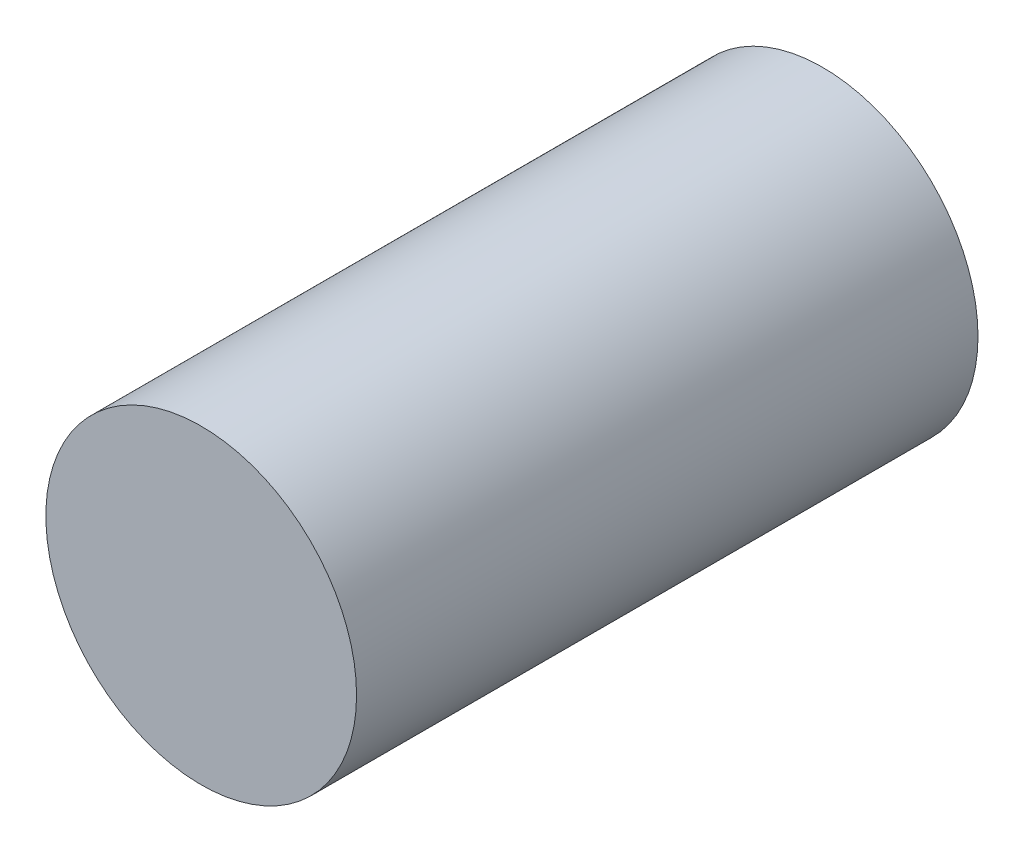
SolidWorks part; units mm, degrees
ref_plane "Front Plane" through (0, 0, 0) normal (0, 0, 1) x (1, 0, 0)
ref_plane "Top Plane" through (0, 0, 0) normal (0, 1, 0) x (1, 0, 0)
ref_plane "Right Plane" through (0, 0, 0) normal (1, 0, 0) x (0, 0, -1)
sketch "Sketch1" plane through (0, 0, 0) normal (0, 0, 1) x (1, 0, 0)
  circle A0 centre (0, 0) radius 12.5
  dimension "D1" = 25
extrude "Boss-Extrude1" add sketch "Sketch1" along normal blind 50
ref_axis "Axis1" through (0, 0, 50) along (0, 0, -1)
